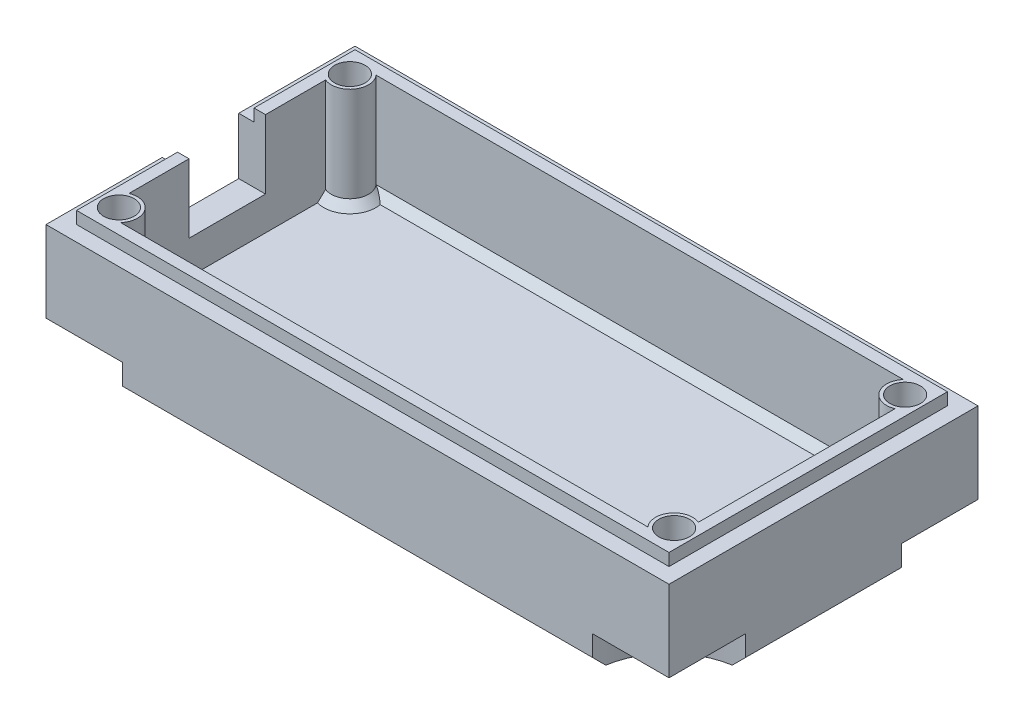
SolidWorks part; units mm, degrees
material "Калифорния"
ref_plane "Спереди" through (0, 0, 0) normal (0, 0, 1) x (1, 0, 0)
ref_plane "Сверху" through (0, 0, 0) normal (0, 1, 0) x (1, 0, 0)
ref_plane "Справа" through (0, 0, 0) normal (1, 0, 0) x (0, 0, -1)
sketch "Эскиз1" plane through (0, 0, 0) normal (0, 1, 0) x (1, 0, 0)
  line L1 (-20.365, -10.1) -> (20.365, -10.1)
  line L2 (-20.365, -10.1) -> (-20.365, 10.1)
  line L3 (-20.365, 10.1) -> (20.365, 10.1)
  line L4 (20.365, -10.1) -> (20.365, 10.1)
  line L5 (-20.365, -10.1) -> (20.365, 10.1) construction
  line L6 (-20.365, 10.1) -> (20.365, -10.1) construction
  point P0 (0, 0)
extrude "Бобышка-Вытянуть1" add sketch "Эскиз1" along normal blind 8.25
shell "Оболочка1" thickness 1.75 removed face at (0, 8.25, 0)
sketch "Эскиз2" plane through (0, 1.75, 0) normal (0, 1, 0) x (1, 0, 0)
  line L0 (18.615, 8.35) -> (-18.615, 8.35) construction
  line L1 (18.615, -8.35) -> (-18.615, -8.35)
  line L2 (18.615, -8.35) -> (18.615, 8.35)
  line L3 (18.615, 8.35) -> (-18.615, 8.35)
  line L4 (-18.615, -8.35) -> (-18.615, 8.35)
  line L5 (18.615, -8.35) -> (-18.615, 8.35) construction
  line L6 (18.615, 8.35) -> (-18.615, -8.35) construction
  line L7 (-18.615, 8.35) -> (-18.615, -8.35) construction
  point P0 (0, 0)
extrude "Вырез-Вытянуть1" cut sketch "Эскиз2" against normal blind 0.2
sketch "Эскиз3" plane through (0, 8.25, 0) normal (0, 1, 0) x (1, 0, 0)
  line L1 (-19.365, -9.1) -> (19.365, -9.1)
  line L2 (-19.365, -9.1) -> (-19.365, 9.1)
  line L3 (-19.365, 9.1) -> (19.365, 9.1)
  line L4 (19.365, -9.1) -> (19.365, 9.1)
  line L5 (-19.365, -9.1) -> (19.365, 9.1) construction
  line L6 (-19.365, 9.1) -> (19.365, -9.1) construction
  line L7 (18.615, -8.35) -> (18.615, 8.35) construction
  line L8 (-18.615, -8.35) -> (18.615, -8.35) construction
  point P0 (0, 0)
  dimension "D1" = 0.75
  dimension "D2" = 0.75
extrude "Вырез-Вытянуть2" cut sketch "Эскиз3" against normal blind 0.8 flip side to cut
sketch "Эскиз5" plane through (0, 1.55, 0) normal (0, 1, 0) x (1, 0, 0)
  circle A0 centre (-18.15, 7.55) radius 1.215
  circle A1 centre (-18.15, -7.55) radius 1.215
  circle A2 centre (18.15, -7.55) radius 1.215
  circle A3 centre (18.15, 7.55) radius 1.215
extrude "Бобышка-Вытянуть2" add sketch "Эскиз5" along normal up to vertex (6.7 mm away) up to point (-18.615, 8.25, -8.35)
sketch "Эскиз4" plane through (0, 0, 0) normal (0, -1, 0) x (1, 0, 0)
  line L0 (-17.15, 7.55) -> (17.15, 7.55) construction
  line L1 (18.15, -6.55) -> (18.15, 6.55) construction
  line L2 (-18.15, -6.55) -> (-18.15, 6.55) construction
  line L3 (-17.15, -7.55) -> (17.15, -7.55) construction
  line L6 (-18.15, 7.55) -> (18.15, -7.55) construction
  line L7 (-18.15, -7.55) -> (18.15, 7.55) construction
  circle A0 centre (-18.15, 7.55) radius 1
  circle A1 centre (-18.15, -7.55) radius 1
  circle A2 centre (18.15, 7.55) radius 1
  circle A3 centre (18.15, -7.55) radius 1
  point P16 (0, 0)
extrude "Вырез-Вытянуть3" cut sketch "Эскиз4" against normal blind 20.8
sketch "Эскиз6" plane through (0, 0, 0) normal (0, -1, 0) x (1, 0, 0)
  circle A0 centre (-20.365, -10.1) radius 5
  circle A1 centre (20.365, -10.1) radius 5
  circle A2 centre (-20.365, 10.1) radius 5
  circle A3 centre (20.365, 10.1) radius 5
extrude "Вырез-Вытянуть4" cut sketch "Эскиз6" against normal blind 1.35
chamfer "Фаска2" distance 0.8 angle 45 12 edges at (17.865, 1.35, 10.1) (20.365, 1.35, 7.6) (20.365, 0, 0) (20.365, 1.35, -7.6) (17.865, 1.35, -10.1) (0, 0, 10.1) (-17.865, 1.35, 10.1) (-20.365, 1.35, 7.6) (-20.365, 1.35, -7.6) (-17.865, 1.35, -10.1) (0, 0, -10.1) (-20.365, 0, 0)
chamfer "Фаска3" distance 0.5 angle 45 7 edges at (-17.1628, 1.55, 6.8417) (0, 1.55, 8.35) (17.1628, 1.55, 6.8417) (18.615, 1.55, 0) (17.1628, 1.55, -6.8417) (0, 1.55, -8.35) (-17.1628, 1.55, -6.8417)
sketch "Эскиз7" plane through (0, 8.25, 0) normal (0, 1, 0) x (1, 0, 0)
  line L0 (-18.615, 5.8992) -> (-18.615, -5.8992) construction
  line L1 (-16.865, -2.5) -> (-20.365, -2.5)
  line L2 (-16.865, -2.5) -> (-16.865, 2.5)
  line L3 (-16.865, 2.5) -> (-20.365, 2.5)
  line L4 (-20.365, -2.5) -> (-20.365, 2.5)
  line L5 (-16.865, -2.5) -> (-20.365, 2.5) construction
  line L6 (-16.865, 2.5) -> (-20.365, -2.5) construction
  line L7 (-20.365, 10.1) -> (-20.365, -10.1) construction
  point P0 (-18.615, 0)
extrude "Вырез-Вытянуть5" cut sketch "Эскиз7" against normal blind 4.5
